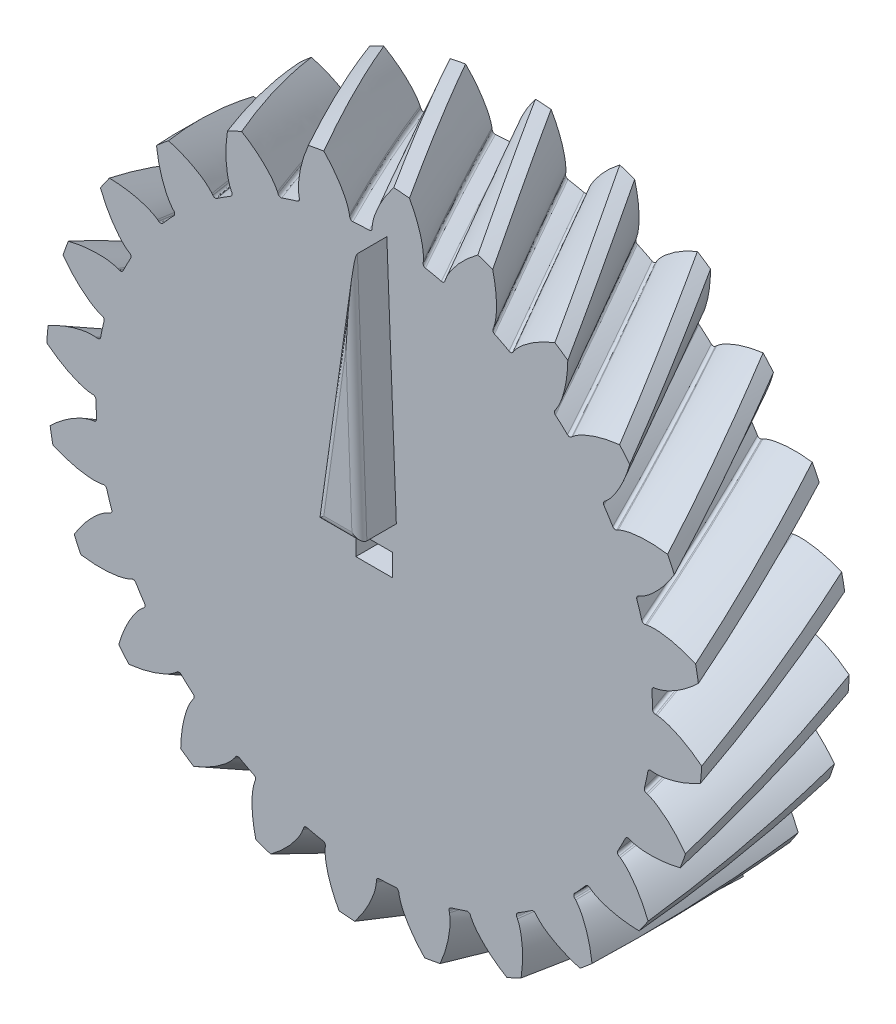
SolidWorks part; units mm, degrees
ref_plane "Front Plane" through (0, 0, 0) normal (0, 0, 1) x (1, 0, 0)
ref_plane "Top Plane" through (0, 0, 0) normal (0, 1, 0) x (1, 0, 0)
ref_plane "Right Plane" through (0, 0, 0) normal (1, 0, 0) x (0, 0, -1)
sketch "Sketch1" plane through (0, 0, 0) normal (0, 0, 1) x (1, 0, 0)
  line L0 (0, 41.5692) -> (-51.4476, 41.5692) construction
  line L1 (0, 41.5692) -> (-49.7878, 20.6445) construction
  line L2 (0, 0) -> (58.6291, 0) construction
  circle A0 centre (0, 0) radius 41.5692 construction
  circle A1 centre (0, 0) radius 38.3223 construction
  circle A2 centre (0, 0) radius 44.5692 construction
  circle A3 centre (0, 0) radius 37.8192
  dimension "D1" = 83.1384
  dimension "D4" = 89.1384
  dimension "D5" = 75.6384
  dimension "D2" = 22.796
extrude "Boss-Extrude1" add sketch "Sketch1" along normal blind 20
sketch "Sketch2" plane through (0, 0, 20) normal (0, 0, 1) x (1, 0, 0)
  circle A0 centre (0, 0) radius 41.5692
  dimension "D1" = 83.1384
curve "Helix/Spiral1" pitch 450.9 height 20 turns 0.0444
sketch "Sketch4" plane through (0, 0, 20) normal (0, 0, 1) x (1, 0, 0)
  line L0 (0, 41.5692) -> (-90.4597, 41.5692) construction
  line L1 (0, 41.5692) -> (-51.9056, 19.7545) construction
  line L2 (0, 0) -> (75.8224, 0) construction
  line L3 (0, 0) -> (38.6855, 15.213) construction
  line L4 (0, 0) -> (46.4442, 21.872) construction
  line L5 (32.9512, 19.3589) -> (32.9693, 19.3696)
  line L6 (35.9123, 13.071) -> (35.9321, 13.0782)
  circle A0 centre (0, 0) radius 41.5692 construction
  circle A1 centre (0, 0) radius 38.3223 construction
  circle A2 centre (0, 0) radius 44.5692 construction
  arc A3 (40.7653, 18.0168) -> (39.855, 19.9498) centre (0, 0) ccw
  arc A4 (32.4058, 19.4976) -> (32.9512, 19.3589) centre (32.7485, 19.7038) ccw
  arc A5 (32.9693, 19.3696) -> (33.1398, 19.459) centre (33.9824, 17.6452) cw
  arc A6 (35.9321, 13.0782) -> (36.1096, 13.1527) centre (35.2481, 14.9576) ccw
  arc A8 (35.6719, 12.5623) -> (35.9123, 13.071) centre (36.0491, 12.6951) cw
  arc A9 (35.6719, 12.5623) -> (32.4058, 19.4976) centre (0, 0) ccw
  spline S0 degree 3 poles (36.1096, 13.1527) (36.2527, 13.221) (36.9042, 13.5706) (38.2391, 14.6554) (39.6294, 16.2526) (40.4741, 17.5328) (40.7653, 18.0168) knots 0.011706 0.011706 0.011706 0.011706 0.063015 0.251582 0.564553 0.747319 0.747319 0.747319 0.747319
  spline S1 degree 3 poles (33.1398, 19.459) (33.2835, 19.5258) (33.9681, 19.8053) (35.6546, 20.1434) (37.7715, 20.1979) (39.2963, 20.0336) (39.855, 19.9498) knots 0.011706 0.011706 0.011706 0.011706 0.063015 0.251582 0.564553 0.747319 0.747319 0.747319 0.747319
  point P7 (38.6855, 15.213)
  dimension "D1" = 83.1384
  dimension "D4" = 89.1384
  dimension "D6" = 2
  dimension "D7" = 2
  dimension "D8" = 0.4
  dimension "D9" = 0.4
  dimension "D2" = 22.796
  dimension "D3" = 3.75
  dimension "D5" = 25.217
ref_plane "Plane1" through (37.6076, 0, 0) normal (1, 0, 0) x (0, 0, -1)
sketch "Sketch5" plane through (37.6076, 0, 0) normal (1, 0, 0) x (0, 0, -1)
  line L0 (-20, 37.8192) -> (-20, -37.8192) construction
  spline S0 degree 3 poles (-20, 17.7106) (-17.778, 18.8751) (-13.3332, 21.1534) (-6.6668, 24.388) (-2.222, 26.4045) (0, 27.3732) knots 0 0 0 0 0.333333 0.666667 1 1 1 1 construction
  point P0 (-20, 17.7106)
ref_plane "Plane2" through (31.2843, 0, 0) normal (1, 0, 0) x (0, 0, -1)
sketch "Sketch6" plane through (31.2843, 0, 0) normal (1, 0, 0) x (0, 0, -1)
  line L0 (0, -37.8192) -> (0, 37.8192) construction
  spline S0 degree 3 poles (-20, 17.7106) (-17.778, 18.8751) (-13.3332, 21.1534) (-6.6668, 24.388) (-2.222, 26.4045) (0, 27.3732) knots 0 0 0 0 0.333333 0.666667 1 1 1 1 construction
  point P0 (0, 27.3732)
ref_plane "Plane3" through (34.446, 22.5419, 0) normal (0.8368, 0.5476, 0) x (0, 0, -1)
sketch "Sketch7" plane through (34.446, 22.5419, 0) normal (0.8368, 0.5476, 0) x (0, 0, -1)
  line L0 (-20, -5.7738) -> (0, 5.7738) construction
sketch "Sketch8" plane through (34.446, 22.5419, 0) normal (0.8368, 0.5476, 0) x (0, 0, -1)
  line L0 (-20, -5.7738) -> (0, 5.7738) construction
  line L1 (0, 5.7738) -> (14.3631, 14.0669) construction
  line L2 (0, 5.7738) -> (24.9369, 5.7738) construction
  dimension "D1" = 30.001
sweep "Sweep1" add profiles "Sketch4" path "Helix/Spiral1"
pattern_circular "CirPattern1" count 24 over 360 of "Sweep1"
sketch "Sketch9" plane through (0, 0, 20) normal (0, 0, 1) x (1, 0, 0)
  line L1 (2.5, 1.5) -> (-2.5, 1.5)
  line L2 (2.5, 1.5) -> (2.5, -1.5)
  line L3 (2.5, -1.5) -> (-2.5, -1.5)
  line L4 (-2.5, 1.5) -> (-2.5, -1.5)
  circle A0 centre (0, 0) radius 0.6699 construction
  dimension "D1" = 5
  dimension "D2" = 3
  dimension "D3" = 2.5
  dimension "D4" = 1.5
extrude "Cut-Extrude1" cut sketch "Sketch9" against normal through all
sketch "Sketch10" plane through (0, 0, 20) normal (0, 0, 1) x (1, 0, 0)
  line L0 (3, 5.105) -> (-3, 5.105)
  line L1 (-3, 5.105) -> (1.7101, 38.2522)
  line L2 (1.7101, 38.2522) -> (3, 5.105)
extrude "Boss-Extrude2" add sketch "Sketch10" along normal blind 5
fillet "Fillet1" radius 1 3 edges at (0, 5.105, 25) (-0.645, 21.6786, 25) (2.355, 21.6786, 25)
